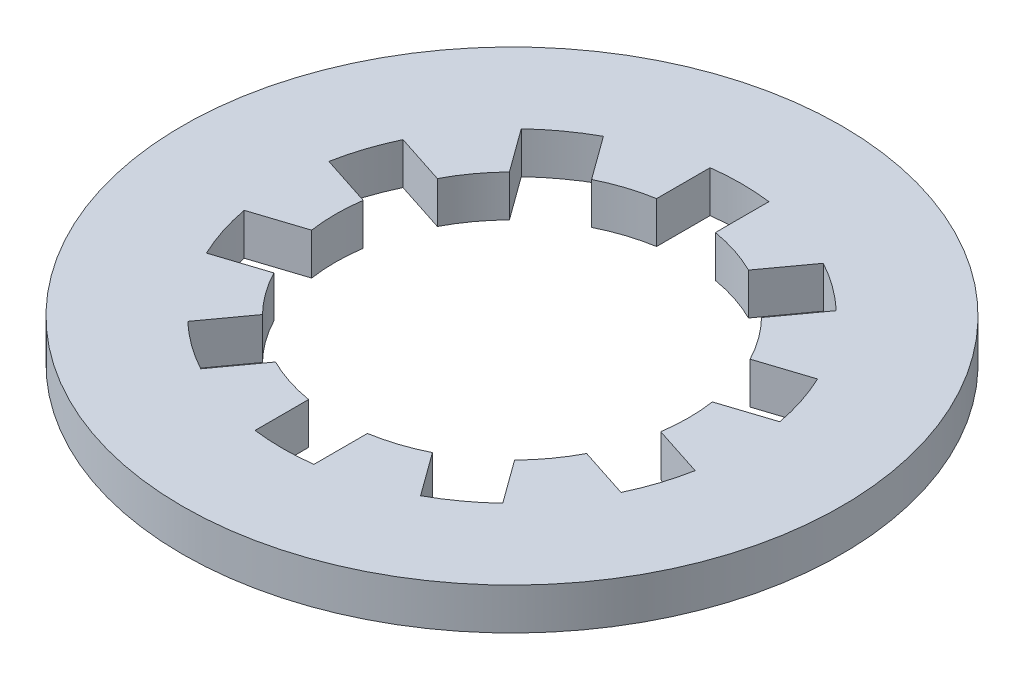
SolidWorks part; units mm, degrees
ref_plane "Front Plane" through (0, 0, 0) normal (0, 0, 1) x (1, 0, 0)
ref_plane "Top Plane" through (0, 0, 0) normal (0, 1, 0) x (1, 0, 0)
ref_plane "Right Plane" through (0, 0, 0) normal (1, 0, 0) x (0, 0, -1)
sketch "Sketch1" plane through (0, 0, 0) normal (0, 1, 0) x (1, 0, 0)
  line L0 (0, 0) -> (0, 7.5854) construction
  circle A0 centre (0, 0) radius 4.8387
  circle A1 centre (0, 0) radius 2.5908
  dimension "B" = 9.6774
  dimension "A" = 5.1816
extrude "Extrude1" add sketch "Sketch1" along normal blind 0.6096
sketch "Sketch2" plane through (0, 0.6096, 0) normal (0, 1, 0) x (-1, 0, 0)
  line L0 (0, 0) -> (0, 9.0768) construction
  line L3 (-0.4318, 3.3402) -> (-0.4318, 2.5546)
  line L5 (0.4318, 3.3402) -> (0.4318, 2.5546)
  circle A0 centre (0, 0) radius 2.5908 construction
  arc A1 (0.4318, 2.5546) -> (-0.4318, 2.5546) centre (0, 0) ccw
  arc A2 (0.4318, 3.3402) -> (-0.4318, 3.3402) centre (0, 0) ccw
  dimension "D1" = 3.368
  dimension "D2" = 0.8636
extrude "Cut-Extrude1" cut sketch "Sketch2" against normal through all
ref_axis "Axis1" through (0, 4.5164, 0) along (0, -1, 0)
pattern_circular "CirPattern1" count 10 over 360 about axis through (0, 4.5164, 0) along (0, -1, 0) of "Cut-Extrude1"
pattern_circular "CirPattern2" [suppressed] count 9 over 360 about axis through (0, 4.5164, 0) along (0, -1, 0) of bodies 102
equation "\"D1@Sketch2\" = \"A@Sketch1\" * 0.65"
equation "\"D2@Sketch2\" = \"A@Sketch1\"/6"
